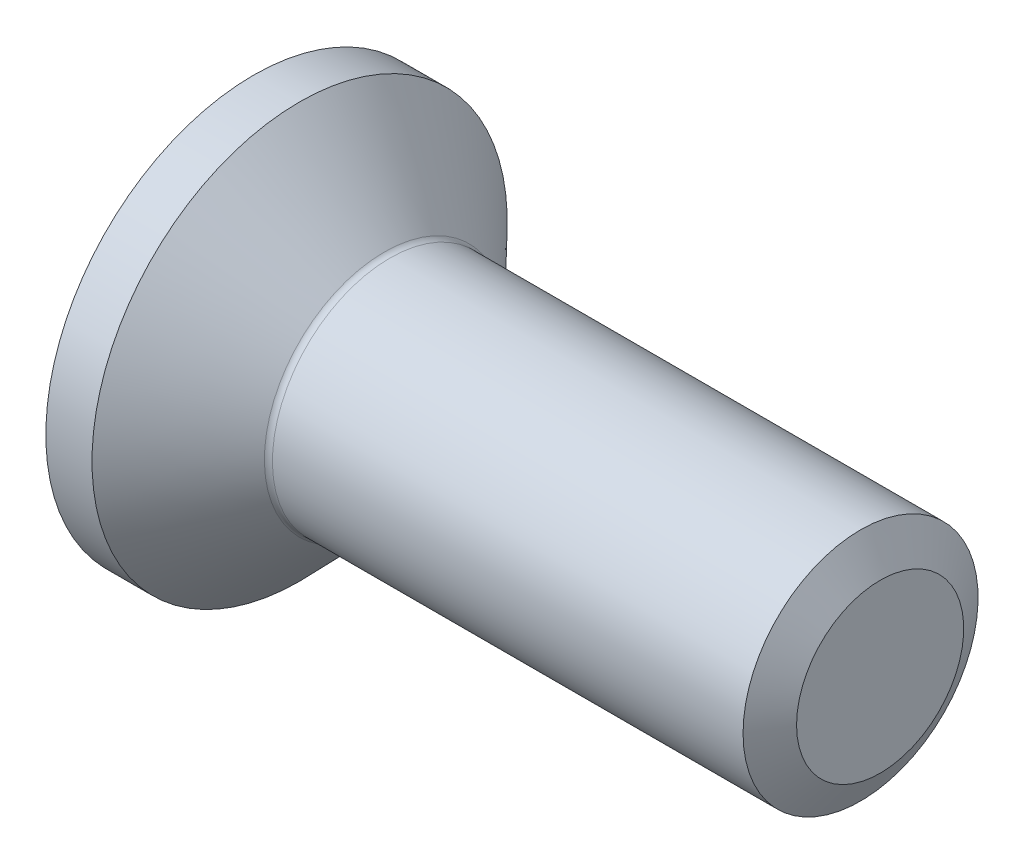
SolidWorks part; units mm, degrees
ref_plane "前视基准面" through (0, 0, 0) normal (0, 0, 1) x (1, 0, 0)
ref_plane "上视基准面" through (0, 0, 0) normal (0, 1, 0) x (1, 0, 0)
ref_plane "右视基准面" through (0, 0, 0) normal (1, 0, 0) x (0, 0, -1)
sketch "尺寸草图" plane through (0, 0, 0) normal (0, 0, 1) x (1, 0, 0)
  line L0 (0, 0) -> (16, 0) construction
  line L1 (16, 0) -> (16, 1.5) construction
  line L2 (16, 1.5) -> (15.5, 1.5) construction
  line L3 (15.5, 1.5) -> (4, 1.5) construction
  line L4 (0, 3.36) -> (1.86, 3.36) construction
  line L5 (1.86, 3.36) -> (1.96, 3.36) construction
  point P3 (16, 1.65)
  point P7 (0, 3.36)
  point P8 (0, 1.5)
  point P9 (0, 2.3)
  point P13 (0, 1)
  point P15 (1.1, 3.36)
  point P16 (1.71, 3.36)
  dimension "l" = 16
  dimension "d" = 3
  dimension "P" = 0.5
  dimension "b" = 12
  dimension "da" = 3.3
  dimension "dk" = 6.72
  dimension "ds" = 3
  dimension "e" = 2.3
  dimension "k" = 1.86
  dimension "r" = 0.1
  dimension "s" = 2
  dimension "t" = 1.1
  dimension "w" = 0.25
sketch "草图1" plane through (0, 0, 0) normal (0, 0, 1) x (1, 0, 0)
  line L0 (0, 1.5) -> (-6.2576, 1.5)
  line L1 (-6.3295, 1.5305) -> (-7.4105, 2.65)
  line L2 (-7.4105, 2.65) -> (-8, 2.65)
  line L3 (-8, 2.65) -> (-8, 0)
  line L4 (-8, 0) -> (0, 0)
  line L5 (0, 0) -> (0, 1.5)
  line L6 (0, 0) -> (-8, 0) construction
  arc A0 (-6.2576, 1.5) -> (-6.3295, 1.5305) centre (-6.2576, 1.6) cw
  point P9 (-6.3, 1.5)
  dimension "r" = 0.1
  dimension "k" = 1.7
  dimension "dk" = 5.3
  dimension "l" = 8
  dimension "D5" = 46
  dimension "d" = 3
revolve "旋转1" add sketch "草图1" angle 360 about L6
cosmetic thread "装饰螺纹线1" parameters "b"=12, "D2"=2.4
sketch "草图2" plane through (-8, 0, 0) normal (-1, 0, 0) x (0, 0, 1)
  line L0 (0, 0) -> (0, 1.5) construction
  line L1 (0, 1.1547) -> (-1, 0.5774)
  line L2 (-1, 0.5774) -> (-1, -0.5774)
  line L3 (-1, -0.5774) -> (0, -1.1547)
  line L4 (0, -1.1547) -> (1, -0.5774)
  line L5 (1, -0.5774) -> (1, 0.5774)
  line L6 (1, 0.5774) -> (0, 1.1547)
  circle A0 centre (0, 0) radius 1 construction
  point P1 (0, 1.1453)
  dimension "s" = 2
  dimension "e" = 2.3
extrude "切除-拉伸1" cut sketch "草图2" against normal blind 1.86
sketch "草图6" plane through (0, 0, 0) normal (0, 0, 1) x (1, 0, 0)
  line L0 (-6.9, 1.1547) -> (-6.2333, 0)
  line L1 (-6.2333, 0) -> (-5.84, 0)
  line L2 (-5.84, 0) -> (-5.84, 1.1547)
  line L3 (-5.84, 1.1547) -> (-6.9, 1.1547)
  line L4 (-8, 0) -> (-6.14, 0) construction
  line L5 (-8, 0) -> (-10.3, 0) construction
  dimension "D1" = 60
  dimension "t" = 1.1
  dimension "t1" = 1.86
  dimension "e-s" = 0.3
  dimension "e" = 2.3
revolve "旋转2" add sketch "草图6" angle 360 about L4
sketch "草图7" plane through (0, 0, 0) normal (0, 0, 1) x (1, 0, 0)
  line L0 (-8, 1.1547) -> (-8, 0)
  line L1 (-8, 0) -> (-7.7, 0)
  line L2 (-7.7, 0) -> (-8, 1.1547)
  line L3 (-8, 0) -> (-7.7, 0) construction
  dimension "e-s*1.1" = 0.3
revolve "切除-旋转2" cut sketch "草图7" angle 360 about L3
sketch "草图4" plane through (0, 0, 0) normal (0, 0, 1) x (1, 0, 0)
  line L0 (-0.25, 1.5) -> (0, 1.067)
  line L1 (0, -1.5) -> (0, 1.5) construction
  line L2 (0, 1.067) -> (0.25, 1.5)
  line L3 (0.25, 1.5) -> (-0.25, 1.5)
  line L4 (-0.25, 0) -> (0.25, 0) construction
  dimension "d" = 3
  dimension "p" = 0.5
revolve "切除-旋转1" cut sketch "草图4" angle 360 about L4
ref_axis "基准轴1" through (-21.1715, 0, 0) along (1, 0, 0)
pattern_linear "阵列(线性)2" [suppressed] count 24 spacing 0.5 along (-1, 0, 0) of bodies 104
